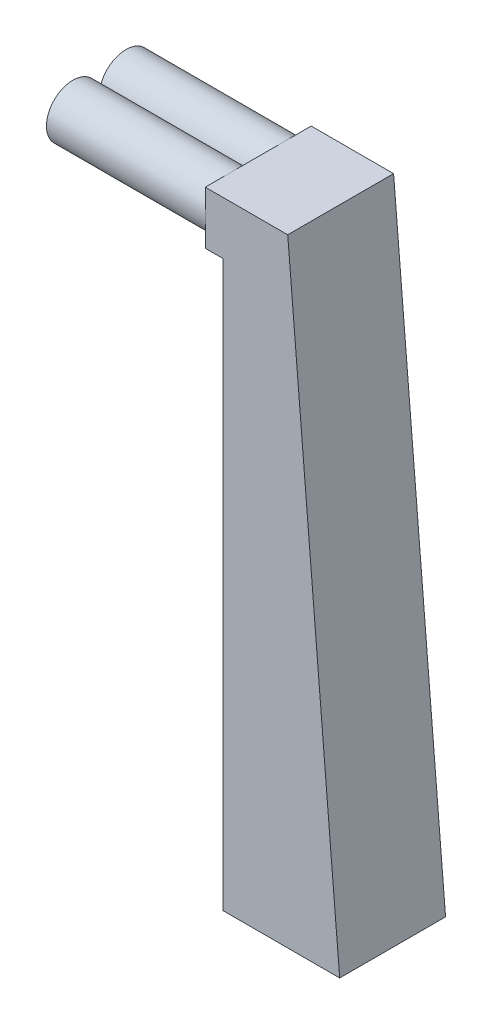
SolidWorks part; units mm, degrees
ref_plane "Piano frontale" through (0, 0, 0) normal (0, 0, 1) x (1, 0, 0)
ref_plane "Piano superiore" through (0, 0, 0) normal (0, 1, 0) x (1, 0, 0)
ref_plane "Piano destro" through (0, 0, 0) normal (1, 0, 0) x (0, 0, -1)
sketch "Schizzo2" plane through (0, 0, 0) normal (0, 0, 1) x (1, 0, 0)
  line L0 (-15.3842, 0) -> (50.7838, 0)
  line L1 (50.7838, 0) -> (21.3359, 350)
  line L2 (21.3359, 350) -> (-15.3842, 350)
  line L3 (-15.3842, 350) -> (-15.3842, 0)
  dimension "D1" = 350
extrude "Estrusione-Estrusione1" add sketch "Schizzo2" along normal blind 30 and the other way blind 30
sketch "Schizzo3" plane through (-15.3842, 0, 0) normal (-1, 0, 0) x (0, 0, 1)
  line L0 (-30, 335) -> (0, 335) construction
  line L5 (-0.0327, 335.9903) -> (0.0327, 335.9903)
  line L6 (-0.0272, 334.0978) -> (0.0272, 334.0978)
  line L14 (0, 335) -> (30, 335) construction
  line L15 (30, 350) -> (30, 0) construction
  arc A0 (-0.0327, 335.9903) -> (-0.0272, 334.0978) centre (-15, 335) ccw
  arc A1 (0.0272, 334.0978) -> (0.0327, 335.9903) centre (15, 335) ccw
extrude "Estrusione-Estrusione2" add sketch "Schizzo3" along normal blind 100 contours A0 L6 A1 L5
sketch "Schizzo4" plane through (-15.3842, 0, 0) normal (-1, 0, 0) x (0, 0, 1)
  line L0 (30, 335) -> (30, 0) construction
  line L1 (-30, 350) -> (30, 350)
  line L2 (-30, 350) -> (-30, 320)
  line L3 (-30, 320) -> (30, 320)
  line L4 (30, 350) -> (30, 320)
  arc A0 (0.0272, 334.0978) -> (0.0327, 335.9903) centre (15, 335) ccw construction
extrude "Estrusione-Estrusione3" add sketch "Schizzo4" along normal blind 10
